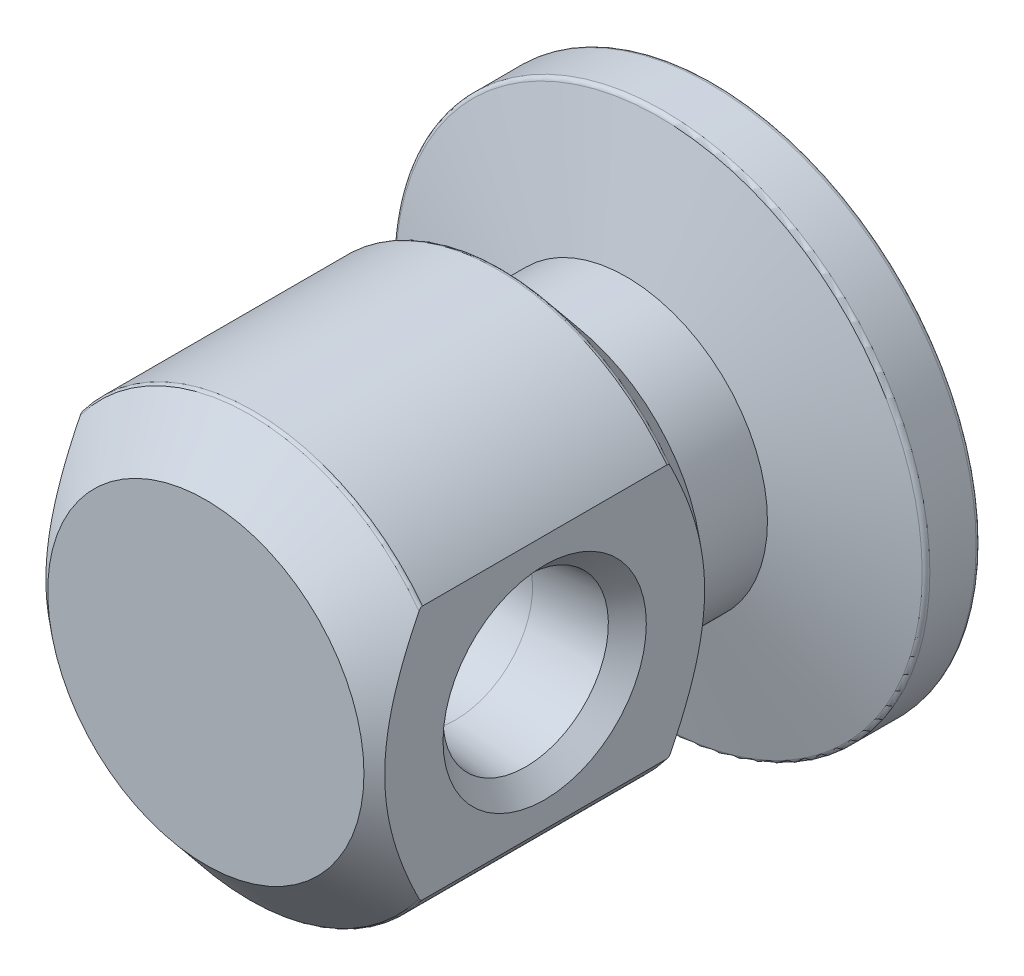
SolidWorks part; units mm, degrees
ref_plane "Front Plane" through (0, 0, 0) normal (0, 0, 1) x (1, 0, 0)
ref_plane "Top Plane" through (0, 0, 0) normal (0, 1, 0) x (1, 0, 0)
ref_plane "Right Plane" through (0, 0, 0) normal (1, 0, 0) x (0, 0, -1)
ref_axis "Axis1" through (0, 0, -23.6792) along (0, 0, 1)
sketch "Sketch4" plane through (0, 0, 0) normal (0, 0, 1) x (1, 0, 0)
  line L1 (-7.9502, 7.9375) -> (19.05, 7.9375) construction
  line L2 (-7.9502, 7.9375) -> (-7.9502, -7.9375) construction
  line L3 (-7.9502, -7.9375) -> (19.05, -7.9375) construction
  line L4 (19.05, 7.9375) -> (19.05, -7.9375) construction
  circle A0 centre (0, 0) radius 15.875
  point P4 (-7.9502, 0)
  dimension "D4" = 31.75
  dimension "D1" = 15.875
  dimension "D2" = 7.9502
  dimension "D3" = 19.05
extrude "Boss-Extrude1" add sketch "Sketch4" along normal blind 12.7 and the other way blind 25.4
sketch "Sketch5" plane through (0, 0, 0) normal (0, 0, 1) x (1, 0, 0)
  line L1 (12.8316, 0) -> (6.4158, 11.1125)
  line L2 (6.4158, 11.1125) -> (-6.4158, 11.1125)
  line L3 (-6.4158, 11.1125) -> (-12.8316, 0)
  line L4 (-12.8316, 0) -> (-6.4158, -11.1125)
  line L5 (-6.4158, -11.1125) -> (6.4158, -11.1125)
  line L6 (6.4158, -11.1125) -> (12.8316, 0)
  circle A0 centre (0, 0) radius 11.1125 construction
  dimension "D1" = 22.225
extrude "Cut-Extrude1" [suppressed] cut sketch "Sketch5" against normal mid plane 25.4 flip side to cut
sketch "Sketch1" plane through (0, 0, 0) normal (-1, 0, 0) x (0, 0, 1)
  line L0 (-16.256, 3.175) -> (3.175, 3.175)
  line L1 (-53.5881, 25.4) -> (-53.5881, 0)
  line L2 (-53.5881, 25.4) -> (15.2654, 25.4)
  line L3 (-19.05, 14.986) -> (-19.05, 8.636)
  line L4 (-19.05, 8.636) -> (-16.256, 8.636)
  line L5 (-16.256, 8.636) -> (-16.256, 3.175)
  line L6 (-10.3242, 7.9375) -> (-9.6684, 7.9375)
  line L7 (-9.6684, 7.9375) -> (-9.6684, 8.7192)
  line L8 (24.5276, 0) -> (17.5841, 0) construction
  line L9 (3.175, 3.175) -> (5.0827, 0)
  line L10 (5.0827, 0) -> (-53.5881, 0)
  line L11 (-19.05, 14.986) -> (-16.002, 14.986)
  line L12 (-16.002, 14.986) -> (-14.1134, 7.9375)
  line L13 (-14.1134, 7.9375) -> (-10.3242, 7.9375)
  line L15 (-9.6684, 8.7192) -> (-6.9887, 11.9126)
  line L18 (-6.9887, 11.9126) -> (6.9887, 11.9126)
  line L19 (6.9887, 11.9126) -> (9.525, 8.89)
  line L20 (9.525, 8.89) -> (9.525, 0)
  line L21 (9.525, 0) -> (15.2654, 0)
  line L22 (15.2654, 0) -> (15.2654, 25.4)
  point P7 (0, 11.9126)
  dimension "D1" = 6.35
  dimension "D2" = 50.8
  dimension "D3" = 50
  dimension "D4" = 9.525
  dimension "D5" = 50
  dimension "D6" = 59
  dimension "D7" = 2.794
  dimension "D8" = 17.272
  dimension "D9" = 3.175
  dimension "D10" = 19.05
  dimension "D11" = 3.048
  dimension "D12" = 15.875
  dimension "D13" = 15
  dimension "D14" = 29.972
  dimension "D15" = 4.445
  dimension "D17" = 23.8252
  dimension "D18" = 17.78
revolve "Cut-Revolve2" cut sketch "Sketch1" angle 360 about L8
sketch "Sketch7" plane through (0, 0, 0) normal (0, 1, 0) x (1, 0, 0)
  line L0 (-14.986, 15.723) -> (-8.0645, 13.8684)
  line L1 (-8.0645, 13.8684) -> (-8.0645, 10.5918)
  line L2 (-9.0029, 9.8044) -> (-11.9126, 7.3629)
  line L3 (-11.9126, 7.3629) -> (-11.9126, 19.05)
  line L4 (0, 0) -> (0, 21.0639) construction
  line L5 (-11.9126, 19.05) -> (-1.0923, 19.05)
  line L6 (8.636, 19.05) -> (-8.636, 19.05) construction
  line L7 (-11.9126, 8.1918) -> (-9.9908, 9.8044)
  line L8 (0, 19.05) -> (-18.1315, 19.05)
  line L9 (-8.0645, 9.8044) -> (-9.9908, 9.8044)
  line L10 (-8.0645, 9.8044) -> (-8.0645, 10.5918)
  dimension "D1" = 130
  dimension "D2" = 105
  dimension "D3" = 8.0645
  dimension "D4" = 5.1816
  dimension "D5" = 3.2766
  dimension "D6" = 0.635
  dimension "D7" = 11.9126
  dimension "D8" = 14.986
  dimension "D9" = 4.064
  dimension "D10" = 3.7984
chamfer "Chamfer1" distance 0.254 angle 45 1 edges at (8.636, 0, -19.05)
fillet "Fillet1" radius 0.254 4 edges at (11.9126, 0, 6.9887) (11.9126, 0, -6.9887) (14.986, 0, -19.05) (14.986, 0, -16.002)
sketch "Sketch6" plane through (0, 0, 0) normal (0, 0, 1) x (1, 0, 0)
  line L0 (-4.7752, 0) -> (22.225, 0)
  line L1 (22.225, 0) -> (22.225, -12.7)
  line L3 (9.525, -5.715) -> (8.4582, -4.6482)
  line L4 (8.4582, -4.6482) -> (4.5388, -4.3053)
  line L5 (4.5388, -4.3053) -> (-2.1883, -4.3053)
  line L6 (-2.1883, -4.3053) -> (-4.7752, 0)
  line L7 (22.225, 0) -> (34.925, 0) construction
  line L9 (9.525, -5.715) -> (9.525, -12.7)
  line L10 (9.525, -12.7) -> (22.225, -12.7)
  dimension "D1" = 11.43
  dimension "D2" = 5
  dimension "D3" = 8.6106
  dimension "D4" = 59
  dimension "D5" = 9.2964
  dimension "D6" = 4.7752
  dimension "D7" = 45
  dimension "D8" = 9.525
  dimension "D9" = 25.4
revolve "Cut-Revolve3" cut sketch "Sketch6" angle 360 about L7
pattern_circular "CirPattern1" count 2 over 360 about axis through (0, 0, -23.6792) along (0, 0, 1) of "Cut-Revolve3"
